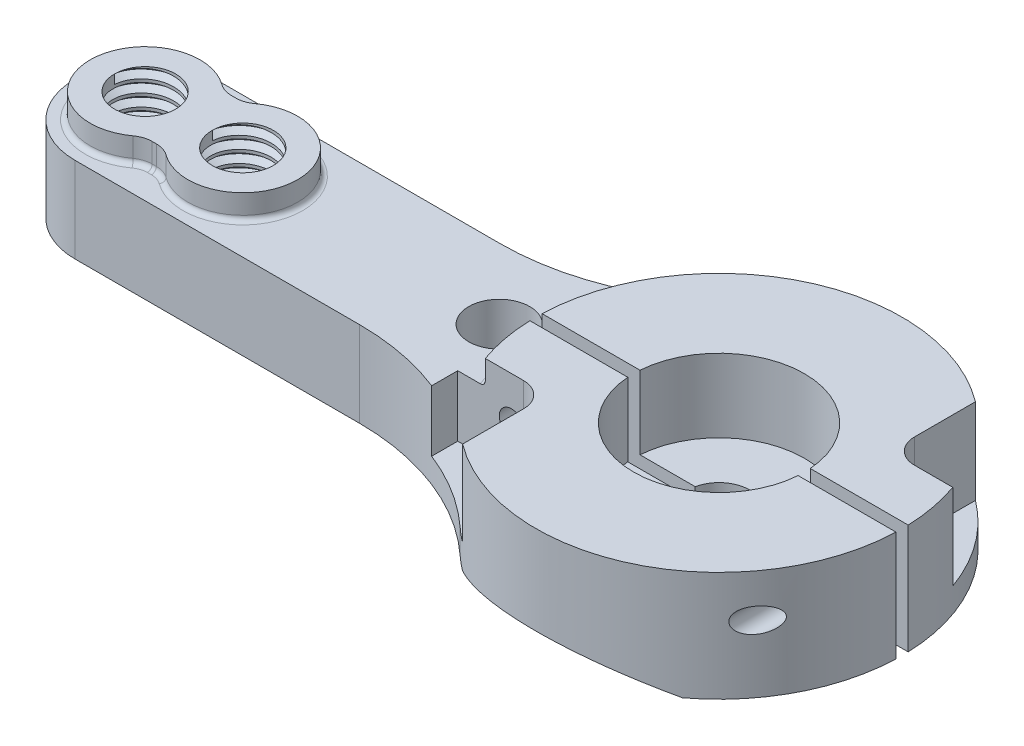
SolidWorks part; units mm, degrees
ref_plane "Front Plane" through (0, 0, 0) normal (0, 0, 1) x (1, 0, 0)
ref_plane "Top Plane" through (0, 0, 0) normal (0, 1, 0) x (1, 0, 0)
ref_plane "Right Plane" through (0, 0, 0) normal (1, 0, 0) x (0, 0, -1)
sketch "Sketch1" plane through (0, 0, 0) normal (0, 1, 0) x (1, 0, 0)
  line L0 (-23.5, 0) -> (0, 0) construction
  line L1 (-23.5, 2.875) -> (-11.8526, 2.875)
  line L2 (-23.5, 2.875) -> (0, 2.875) construction
  line L3 (-23.5, -2.875) -> (0, -2.875) construction
  line L4 (-23.5, -2.875) -> (-11.8526, -2.875)
  line L5 (-9, 0) -> (0, 0) construction
  line L6 (-9, 0.5) -> (0, 0.5) construction
  line L7 (-9, -0.5) -> (0, -0.5) construction
  arc A0 (-23.5, 2.875) -> (-23.5, -2.875) centre (-23.5, 0) ccw construction
  arc A1 (0, -2.875) -> (0, 2.875) centre (0, 0) ccw construction
  circle A2 centre (0, 0) radius 7.5 construction
  arc A3 (-23.5, 2.875) -> (-23.5, -2.875) centre (-23.5, 0) ccw
  arc A4 (-5.0797, 5.5179) -> (-5.0797, -5.5179) centre (0, 0) cw
  arc A5 (-11.8526, -2.875) -> (-5.0797, -5.5179) centre (-11.8526, -12.875) cw
  arc A6 (-5.0797, 5.5179) -> (-11.8526, 2.875) centre (-11.8526, 12.875) cw
  circle A7 centre (-9, 0) radius 1.5 construction
  arc A8 (-9, 0.5) -> (-9, -0.5) centre (-9, 0) ccw construction
  arc A9 (0, -0.5) -> (0, 0.5) centre (0, 0) ccw construction
  point P4 (-11.75, 0)
  point P18 (-6.9271, -2.875)
  point P21 (-6.9271, 2.875)
  point P24 (-4.5, 0)
  dimension "D3" = 16.5729
  dimension "D5" = 7.5
  dimension "D6" = 10
  dimension "D7" = 10
  dimension "D8" = 3
  dimension "D1" = 23.5
  dimension "D2" = 5.75
  dimension "D4" = 16.5729
  dimension "D9" = 1
extrude "Boss-Extrude1" add sketch "Sketch1" along normal blind 3.5
sketch "Sketch10" plane through (0, 3.5, 0) normal (0, 1, 0) x (1, 0, 0)
  circle A0 centre (0, 0) radius 7.5
extrude "Boss-Extrude3" add sketch "Sketch10" along normal blind 1
sketch "Sketch11" plane through (0, 3.5, 0) normal (0, 1, 0) x (1, 0, 0)
  line L5 (-23.5, 0) -> (-19.5, 0) construction
  line L6 (-21.5, -1.625) -> (-21.5, 1.625) construction
  line L7 (-2.475, 0) -> (2.475, 0) construction
  line L8 (-21.5838, -1.625) -> (-21.4162, -1.625)
  line L9 (-21.5838, 1.625) -> (-21.4162, 1.625)
  circle A0 centre (-23.5, 0) radius 2.25 construction
  circle A1 centre (-19.5, 0) radius 2.25 construction
  arc A2 (-22.1734, -1.8173) -> (-22.1734, 1.8173) centre (-23.5, 0) cw
  arc A3 (-20.8266, 1.8173) -> (-20.8266, -1.8173) centre (-19.5, 0) cw
  arc A4 (-22.1734, -1.8173) -> (-21.5838, -1.625) centre (-21.5838, -2.625) cw
  arc A5 (-20.8266, -1.8173) -> (-21.4162, -1.625) centre (-21.4162, -2.625) ccw
  arc A6 (-21.4162, 1.625) -> (-20.8266, 1.8173) centre (-21.4162, 2.625) ccw
  arc A7 (-21.5838, 1.625) -> (-22.1734, 1.8173) centre (-21.5838, 2.625) cw
  point P10 (-21.5023, 0)
  point P12 (-21.5, 0)
  point P19 (-21.9438, -1.625)
  point P23 (-21.0562, -1.625)
  point P26 (-21.0562, 1.625)
  point P29 (-21.9438, 1.625)
  dimension "D1" = 4.5
  dimension "D2" = 4.5
  dimension "D4" = 4
  dimension "D10" = 2.25
  dimension "D11" = 2.25
  dimension "D12" = 1
  dimension "D3" = 19.5
  dimension "D5" = 2.0023
  dimension "D6" = 4
  dimension "D7" = 0.8875
  dimension "D8" = 3.25
  dimension "D9" = 0.8875
extrude "Boss-Extrude4" add sketch "Sketch11" along normal blind 1
fillet "Fillet1" radius 0.2 8 edges at (-21.1061, 3.5, 1.6743) (-17.25, 3.5, 0) (-21.1061, 3.5, -1.6743) (-21.5, 3.5, -1.625) (-21.8939, 3.5, -1.6743) (-25.75, 3.5, 0) (-21.8939, 3.5, 1.6743) (-21.5, 3.5, 1.625)
fillet "Fillet2" radius 0.2 1 edges at (-7.5, 3.5, 0)
sketch "Sketch4" plane through (0, 0, 0) normal (0, -1, 0) x (1, 0, 0)
  circle A0 centre (0, 0) radius 5
extrude "Cut-Extrude1" cut sketch "Sketch4" against normal blind 1
sketch "Sketch7" plane through (0, 0, 0) normal (0, -1, 0) x (1, 0, 0)
  line L2 (9, -0.25) -> (-9, -0.25)
  line L3 (9, -0.25) -> (9, 0.25)
  line L4 (-9, -0.25) -> (-9, 0.25)
  line L5 (9, 0.25) -> (-9, 0.25)
  line L6 (9, -0.25) -> (-9, 0.25) construction
  line L7 (-9, -0.25) -> (9, 0.25) construction
  point P1 (0, 0)
  dimension "D1" = 0.25
  dimension "D2" = 9
extrude "Cut-Extrude4" cut sketch "Sketch7" against normal through all
hole_wizard "Tap Drill for M3x0.5 Tap3" positions "Sketch12" profile "Sketch13" hole size "M3x0.5" standard "ANSI Metric" end condition through all
sketch "Sketch12" plane through (0, 0, 0) normal (0, -1, 0) x (-1, 0, 0)
  line L0 (9, -0.25) -> (9, 0.25) construction
  point P0 (0, 0)
  point P3 (19.5, 0)
  point P5 (23.5, 0)
  point P7 (9, 0)
  dimension "D1" = 9
  dimension "D2" = 23.5
  dimension "D3" = 19.5
sketch "Sketch13" plane through (0, 0, 0) normal (1, 0, 0) x (0, 0, -1)
  line L0 (0, 0) -> (0, 4.5)
  line L1 (0, 4.5) -> (1.25, 4.5)
  line L2 (1.25, 4.5) -> (1.25, 0)
  line L5 (1.25, 0) -> (0, 0)
  line L11 (0, -6.35) -> (0, 107.95) construction
  dimension "Thru Hole Dia." = 2.5
  dimension "Thru Hole Depth" = 4.5
sketch "Sketch15" plane through (0, 0, 0) normal (0, 0, 1) x (1, 0, 0)
  line L3 (-6, 2.75) -> (0, 2.75) construction
  line L6 (0, -2.475) -> (0, 2.475) construction
  line L7 (0, 2.75) -> (6, 2.75) construction
  line L8 (8.25, 0) -> (-8.25, 0) construction
  circle A0 centre (-6, 2.75) radius 0.5
  circle A1 centre (6, 2.75) radius 0.5
  dimension "D1" = 1
  dimension "D2" = 1
  dimension "D3" = 6
  dimension "D4" = 2.75
  dimension "D5" = 2.75
extrude "Cut-Extrude5" cut sketch "Sketch15" against normal through all both and the other way through all
sketch "Sketch17" plane through (0, 4.5, 0) normal (0, 1, 0) x (1, 0, 0)
  line L0 (0, -2.475) -> (0, 2.475) construction
  line L1 (-2.475, 0) -> (2.475, 0) construction
  line L2 (0, 0) -> (-0.7258, -2.9109) construction
  line L3 (-0.7258, -2.9109) -> (0, 0)
  line L4 (0, -3) -> (0, 0) construction
  line L5 (-0.7258, -2.9109) -> (-0.3412, -2.7791)
  line L6 (-0.3412, -2.7791) -> (0, -3)
  line L7 (0, 0) -> (0, -3)
  circle A0 centre (0, 0) radius 3 construction
  dimension "D1" = 6
  dimension "D2" = 3
  dimension "D3" = 14
  dimension "D4" = 3
  dimension "D5" = 2.8
extrude "Cut-Extrude6" cut sketch "Sketch17" against normal blind 3
pattern_circular "CirPattern1" count 26 over 360 about axis through (0, 3.5, 0) along (0, -1, 0) of "Cut-Extrude6"
sketch "Sketch18" plane through (0, 0, 0) normal (1, 0, 0) x (0, 0, -1)
  line L0 (-6, 0) -> (-7.5, 0.866)
  line L2 (8.25, 0) -> (-8.25, 0) construction
  line L3 (-7.5, 0.866) -> (-7.5, 0)
  line L4 (-7.5, 0) -> (-6, 0)
  dimension "D1" = 30
  dimension "D2" = 1.5
  dimension "D3" = 6
extrude "Cut-Extrude7" cut sketch "Sketch18" against normal up to next and the other way up to next
mirror "Mirror1" about plane through (0, 0, 0) normal (0, 0, 1) of "Cut-Extrude7"
sketch "Sketch19" plane through (0, 0, 0) normal (0, 0, 1) x (1, 0, 0)
  line L0 (8.25, 0) -> (-8.25, 0) construction
  line L1 (-8.2, 4.5) -> (-4.5, 4.5)
  line L2 (-8.2, 4.5) -> (-8.2, 1)
  line L3 (-8.2, 1) -> (-4.5, 1)
  line L4 (-4.5, 4.5) -> (-4.5, 1)
  line L5 (7.4958, 4.5) -> (-7.4958, 4.5) construction
  line L6 (0, -2.475) -> (0, 2.475) construction
  point P0 (-6.4098, 2.75)
  dimension "D1" = 1
  dimension "D2" = 3.7
  dimension "D3" = 1.75
  dimension "D4" = 1.7902
  dimension "D5" = 4.5
extrude "Cut-Extrude8" cut sketch "Sketch19" along normal blind 9 from offset 2.5
fillet "Fillet6" radius 1 1 edges at (-4.5, 2.75, 2.5)
pattern_circular "CirPattern2" count 2 over 360 about axis through (0, 3.5, 0) along (0, -1, 0) of "Cut-Extrude8"
fillet "Fillet7" radius 1 1 edges at (4.5, 2.75, -2.5)
thread "Thread1" pitch 0.5 method cut profile "Thread Profile4" start angle 0, offset 0, length 0, pitch 0.5, diameter 2.5
ref_plane "Plane4" through (-24.75, 4.5, 0) normal (0, 0, 1) x (-1, 0, 0)
sketch "Thread Profile4" plane through (-24.75, 4.5, 0) normal (0, 0, 1) x (-1, 0, 0)
  line L0 (0, 0) -> (0, 0.5) construction
  line L1 (0, 0) -> (0.2706, 0.1562)
  line L2 (0.2706, 0.1562) -> (0.2706, 0.2187)
  line L3 (0.2706, 0.2187) -> (0, 0.375)
  line L4 (0.2706, 0.1875) -> (0, 0.1875) construction
  line L11 (0, 0) -> (0, 0.375)
  point P2 (0, 0)
  dimension "Pitch" = 0.5
  dimension "Profile_Angle" = 60
  dimension "Profile_Land" = 0.0625
  dimension "Profile_Height" = 0.2706
thread "Thread2" pitch 0.5 method cut profile "Thread Profile5" start angle 0, offset 0, length 0, pitch 0.5, diameter 2.5
ref_plane "Plane5" through (-20.75, 4.5, 0) normal (0, 0, 1) x (-1, 0, 0)
sketch "Thread Profile5" plane through (-20.75, 4.5, 0) normal (0, 0, 1) x (-1, 0, 0)
  line L0 (0, 0) -> (0, 0.5) construction
  line L1 (0, 0) -> (0.2706, 0.1562)
  line L2 (0.2706, 0.1562) -> (0.2706, 0.2187)
  line L3 (0.2706, 0.2187) -> (0, 0.375)
  line L4 (0.2706, 0.1875) -> (0, 0.1875) construction
  line L11 (0, 0) -> (0, 0.375)
  point P2 (0, 0)
  dimension "Pitch" = 0.5
  dimension "Profile_Angle" = 60
  dimension "Profile_Land" = 0.0625
  dimension "Profile_Height" = 0.2706
sketch "Esquisse1" plane through (0, 1.5, 0) normal (0, 1, 0) x (1, 0, 0)
  circle A0 centre (0, 0) radius 2.9948 construction
  circle A1 centre (0, 0) radius 3.4948
  dimension "D1" = 0.5
extrude "Enlèv. mat.-Extru.1" cut sketch "Esquisse1" along normal through all
